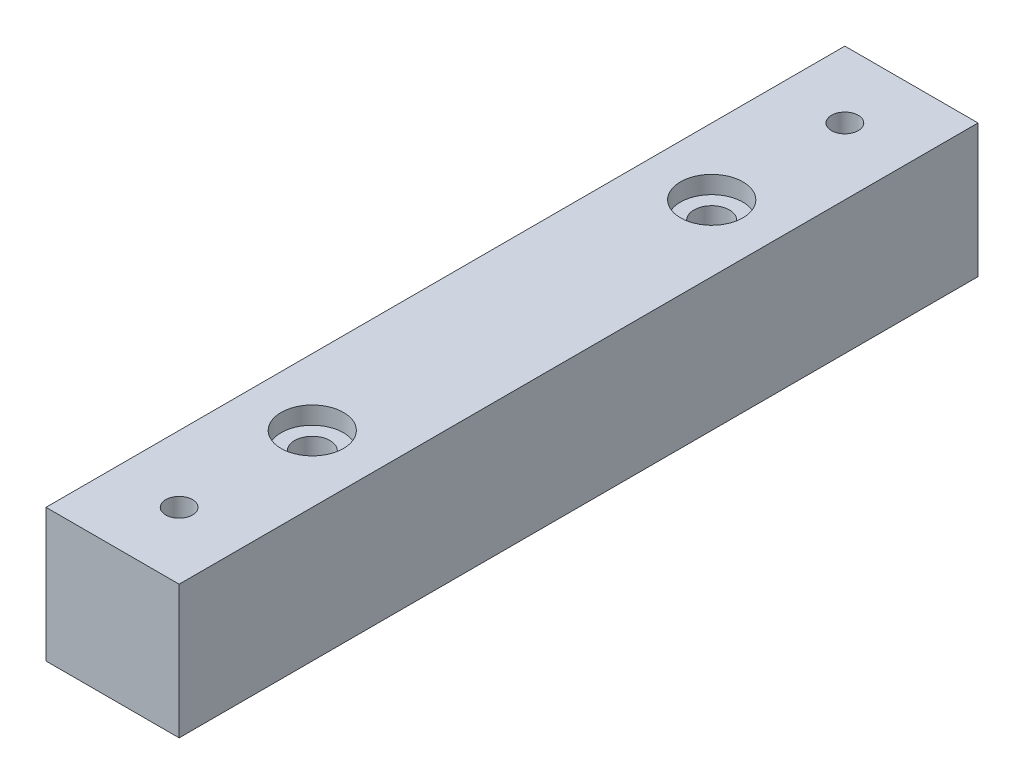
SolidWorks part; units mm, degrees
material "EPDM"
ref_plane "Front Plane" through (0, 0, 0) normal (0, 0, 1) x (1, 0, 0)
ref_plane "Top Plane" through (0, 0, 0) normal (0, 1, 0) x (1, 0, 0)
ref_plane "Right Plane" through (0, 0, 0) normal (1, 0, 0) x (0, 0, -1)
sketch "Sketch1" plane through (0, 0, 0) normal (0, 0, 1) x (1, 0, 0)
  line L1 (-12.7, -12.7) -> (12.7, -12.7)
  line L2 (-12.7, -12.7) -> (-12.7, 12.7)
  line L3 (-12.7, 12.7) -> (12.7, 12.7)
  line L4 (12.7, -12.7) -> (12.7, 12.7)
  line L5 (-12.7, -12.7) -> (12.7, 12.7) construction
  line L6 (-12.7, 12.7) -> (12.7, -12.7) construction
  point P0 (0, 0)
  dimension "D1" = 25.4
  dimension "D2" = 25.4
extrude "Boss-Extrude1" add sketch "Sketch1" along normal blind 152.4
sketch "Sketch2" plane through (0, 12.7, 0) normal (0, 1, 0) x (1, 0, 0)
  line L0 (0, 0) -> (0, -12.7) construction
  line L1 (-12.7, -76.2) -> (12.7, -76.2) construction
  line L2 (-12.7, -152.4) -> (-12.7, 0) construction
  line L3 (12.7, -152.4) -> (12.7, 0) construction
  line L4 (0, 0) -> (0, -15.875) construction
  line L5 (-6.35, -34.925) -> (-6.35, -38.1) construction
  circle A0 centre (0, -12.7) radius 3.175
  circle A1 centre (0, -139.7) radius 3.175
  circle A2 centre (-6.35, -38.1) radius 3.175
  circle A3 centre (-6.35, -114.3) radius 3.175
  dimension "D2" = 6.35
  dimension "D1" = 12.7
extrude "Cut-Extrude1" [suppressed] cut sketch "Sketch2" against normal blind 152.4
sketch "Sketch3" plane through (-12.7, 0, 0) normal (-1, 0, 0) x (0, 0, 1)
  line L0 (0, 0) -> (12.7, 0) construction
  line L1 (152.4, 0) -> (139.7, 0) construction
  line L2 (152.4, 12.7) -> (152.4, -12.7) construction
  circle A0 centre (139.7, 0) radius 3.175
  circle A1 centre (12.7, 0) radius 3.175
  dimension "D3" = 6.35
  dimension "D4" = 6.35
  dimension "D1" = 12.7
  dimension "D2" = 12.7
extrude "Cut-Extrude2" [suppressed] cut sketch "Sketch3" against normal blind 152.4
sketch "Sketch4" [suppressed] plane through (0, 12.7, 0) normal (0, 1, 0) x (1, 0, 0)
  line L0 (0, 0) -> (0, -25.4) construction
  line L1 (-12.7, -25.4) -> (12.7, -25.4)
  line L2 (-12.7, -152.4) -> (-12.7, 0) construction
  line L3 (12.7, -152.4) -> (12.7, 0) construction
  line L4 (12.7, -25.4) -> (12.7, -152.4)
  line L5 (12.7, -152.4) -> (-12.7, -152.4)
  line L6 (-12.7, -152.4) -> (-12.7, -25.4)
  dimension "D1" = 25.4
extrude "Cut-Extrude3" [suppressed] cut sketch "Sketch4" against normal blind 152.4
sketch "Sketch5" [suppressed] plane through (0, 12.7, 0) normal (0, 1, 0) x (1, 0, 0)
  line L0 (0, 0) -> (0, -25.4) construction
  line L1 (-12.7, -76.2) -> (12.7, -76.2) construction
  line L2 (-12.7, -152.4) -> (-12.7, 0) construction
  line L3 (12.7, -152.4) -> (12.7, 0) construction
  line L4 (-12.7, -25.4) -> (12.7, -25.4)
  line L5 (12.7, -25.4) -> (12.7, -127)
  line L6 (-12.7, -25.4) -> (-12.7, -127)
  line L7 (-12.7, -127) -> (12.7, -127)
  dimension "D1" = 25.4
extrude "Cut-Extrude4" [suppressed] cut sketch "Sketch5" against normal blind 152.4 flip side to cut
sketch "Sketch6" plane through (0, 12.7, 0) normal (0, 1, 0) x (1, 0, 0)
  line L0 (12.7, -76.2) -> (-12.7, -76.2) construction
  line L1 (12.7, -152.4) -> (12.7, 0) construction
  line L2 (-12.7, -152.4) -> (-12.7, 0) construction
  line L3 (0, 0) -> (0, -12.7) construction
  line L4 (0, -152.4) -> (0, -139.7) construction
  dimension "D1" = 12.7
hole_wizard "1/4-20 Tapped Hole1" positions "3DSketch1" profile "Sketch7" tap size "1/4-20" standard "Ansi Inch"
sketch3d "3DSketch1"
  point P0 (0, 12.7, 12.7)
  point P3 (0, 12.7, 139.7)
sketch "Sketch7" plane through (0, 12.7, 12.7) normal (1, 0, 0) x (0, 0, 1)
  line L0 (0, 0) -> (0, 20.6338)
  line L1 (0, 20.6338) -> (2.5527, 19.1)
  line L2 (2.5527, 19.1) -> (2.5527, 0)
  line L5 (2.5527, 0) -> (0, 0)
  line L10 (0, 20.6338) -> (-2.5527, 19.1) construction
  line L11 (0, -6.35) -> (0, 107.95) construction
  dimension "Tap Drill Dia." = 5.1054
  dimension "Tap Drill Depth" = 19.1
  dimension "Drill Angle" = 118
sketch "Sketch8" plane through (0, 12.7, 0) normal (0, 1, 0) x (1, 0, 0)
  line L0 (-12.7, -76.2) -> (12.7, -76.2) construction
  line L1 (-12.7, -152.4) -> (-12.7, 0) construction
  line L2 (12.7, -152.4) -> (12.7, 0) construction
  line L3 (0, 0) -> (0, -38.1) construction
  line L4 (0, -152.4) -> (0, -114.3) construction
  dimension "D1" = 38.1
hole_wizard "CBORE for 1/4 Button Head Cap Screw1" positions "3DSketch2" profile "Sketch9" counterbore size "1/4" standard "Ansi Inch" end condition through all
sketch3d "3DSketch2"
  point P0 (0, 12.7, 38.1)
  point P3 (0, 12.7, 114.3)
sketch "Sketch9" plane through (0, 12.7, 38.1) normal (1, 0, 0) x (0, 0, 1)
  line L0 (0, 0) -> (0, 25.4)
  line L1 (0, 25.4) -> (3.3782, 25.4)
  line L3 (3.3782, 25.4) -> (3.3782, 3.3528)
  line L4 (3.3782, 3.3528) -> (5.9538, 3.3528)
  line L5 (5.9538, 3.3528) -> (5.9538, 0)
  line L7 (5.9538, 0) -> (0, 0)
  line L11 (0, -6.35) -> (0, 107.95) construction
  dimension "Thru Hole Dia." = 6.7564
  dimension "Thru Hole Depth" = 25.4
  dimension "C'Bore Dia." = 11.9075
  dimension "C'Bore Depth" = 3.3528
